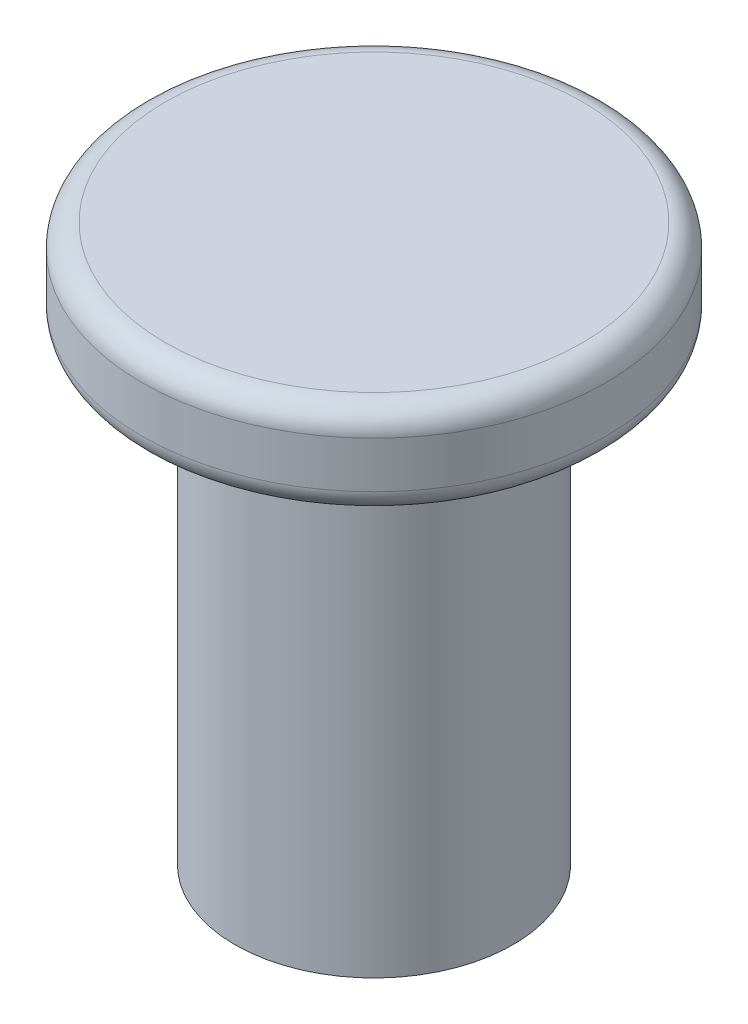
SolidWorks part; units mm, degrees
ref_plane "Front Plane" through (0, 0, 0) normal (0, 0, 1) x (1, 0, 0)
ref_plane "Top Plane" through (0, 0, 0) normal (0, 1, 0) x (1, 0, 0)
ref_plane "Right Plane" through (0, 0, 0) normal (1, 0, 0) x (0, 0, -1)
sketch "Sketch1" plane through (0, 0, 0) normal (0, 1, 0) x (1, 0, 0)
  circle A0 centre (0, 0) radius 2.5
  dimension "D1" = 5
extrude "Boss-Extrude1" add sketch "Sketch1" along normal blind 1
sketch "Sketch3" plane through (0, 0, 0) normal (0, -1, 0) x (1, 0, 0)
  circle A0 centre (0, 0) radius 1.5
  circle A1 centre (0, 0) radius 2.5 construction
  dimension "D1" = 3
  dimension "D2" = 1
extrude "Boss-Extrude3" add sketch "Sketch3" along normal blind 5
fillet "Fillet1" radius 0.25 2 edges at (0, 0, 2.5) (0, 1, 2.5)
hole_wizard "1/16 (0.07874016) Diameter Hole1" positions "Sketch8" profile "Sketch7" hole size "1/16" standard "ANSI Inch"
sketch "Sketch8" plane through (0, -5, 0) normal (0, -1, 0) x (-1, 0, 0)
  point P0 (0, 0)
sketch "Sketch7" plane through (0, -5, 0) normal (1, 0, 0) x (0, 0, -1)
  line L0 (0, 0) -> (0, 3.5)
  line L1 (0, 3.5) -> (1, 2.8991)
  line L2 (1, 2.8991) -> (1, 0)
  line L5 (1, 0) -> (0, 0)
  line L10 (0, 3.5) -> (-1, 2.8991) construction
  line L11 (0, -6.35) -> (0, 107.95) construction
  dimension "Hole Dia." = 2
  dimension "Hole Depth" = 3.5
  dimension "Drill Angle" = 118
fillet "Fillet2" radius 0.15 1 edges at (0, -5, -1)
